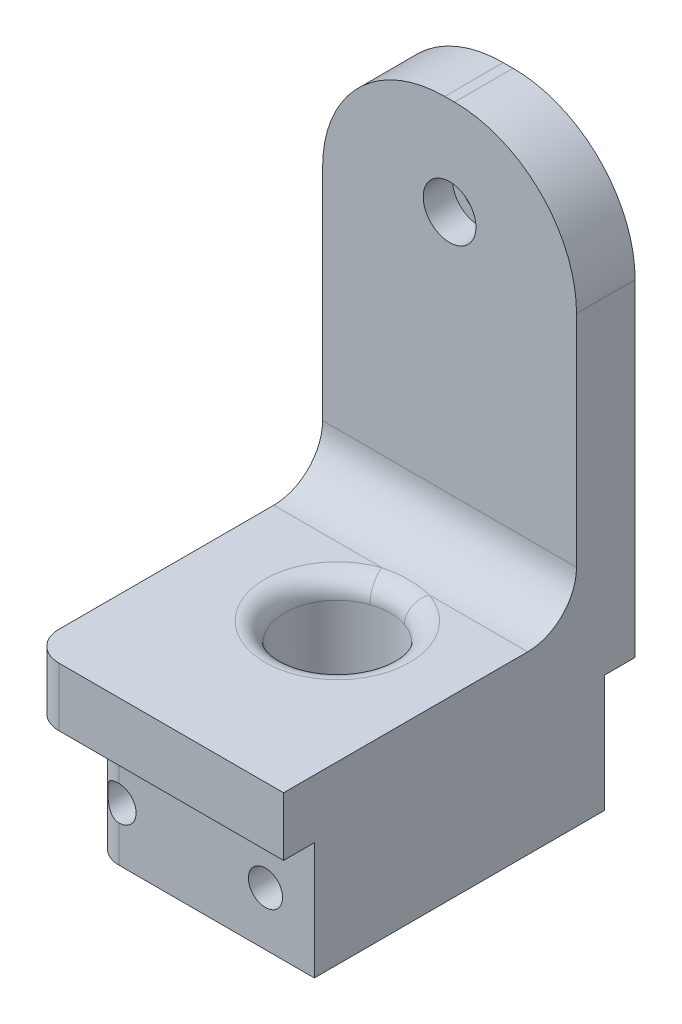
SolidWorks part; units mm, degrees
ref_plane "Front Plane" through (0, 0, 0) normal (0, 0, 1) x (1, 0, 0)
ref_plane "Top Plane" through (0, 0, 0) normal (0, 1, 0) x (1, 0, 0)
ref_plane "Right Plane" through (0, 0, 0) normal (1, 0, 0) x (0, 0, -1)
sketch "Sketch1" plane through (0, -44, 0) normal (0, 1, 0) x (1, 0, 0)
  line L0 (50.2641, 25) -> (50.2641, 28) construction
  line L1 (50.2641, -8) -> (50.2641, 28)
  line L2 (50.2641, -8) -> (27.2641, -8) construction
  line L3 (50.2641, -8) -> (27.2641, -8)
  line L4 (24.2641, -5) -> (24.2641, 25)
  line L5 (27.2641, 28) -> (50.2641, 28)
  arc A0 (27.2641, 28) -> (24.2641, 25) centre (27.2641, 25) ccw construction
  arc A1 (24.2641, -5) -> (27.2641, -8) centre (27.2641, -5) ccw construction
  arc A2 (27.2641, 28) -> (24.2641, 25) centre (27.2641, 25) ccw
  arc A3 (24.2641, -5) -> (27.2641, -8) centre (27.2641, -5) ccw
extrude "Boss-Extrude1" add sketch "Sketch1" along normal blind 6
sketch "Sketch2" plane through (0, -38, 0) normal (0, 1, 0) x (1, 0, 0)
  line L0 (24.2641, 25) -> (24.2641, -5) construction
  line L1 (50.2641, 28) -> (24.2641, 28)
  line L2 (50.2641, 28) -> (50.2641, 22)
  line L3 (50.2641, 22) -> (24.2641, 22)
  line L4 (24.2641, 28) -> (24.2641, 22)
  dimension "D1" = 6
extrude "Boss-Extrude2" add sketch "Sketch2" along normal blind 40
fillet "Fillet1" radius 12.5 2 edges at (24.2641, 2, -25) (50.2641, 2, -25)
sketch "Sketch3" plane through (0, 0, -22) normal (0, 0, 1) x (1, 0, 0)
  circle A0 centre (37.2641, -8) radius 2.7
extrude "Cut-Extrude1" cut sketch "Sketch3" against normal through all
sketch "Sketch4" plane through (0, -44, 0) normal (0, -1, 0) x (1, 0, 0)
  line L3 (50.2641, 4.85) -> (50.2641, -24.85)
  line L6 (50.2641, -24.85) -> (30.2641, -24.85)
  line L7 (27.4141, 2) -> (27.4141, -22)
  line L8 (30.2641, 4.85) -> (50.2641, 4.85)
  arc A4 (27.4141, -22) -> (30.2641, -24.85) centre (30.2641, -22) ccw
  arc A5 (30.2641, 4.85) -> (27.4141, 2) centre (30.2641, 2) ccw
extrude "Boss-Extrude3" add sketch "Sketch4" along normal blind 12
fillet "Fillet2" radius 5 1 edges at (37.2641, -38, -22)
sketch "Sketch5" plane through (0, 0, -24.85) normal (0, 0, -1) x (-1, 0, 0)
  circle A0 centre (-45.2641, -50.5) radius 1.75
  circle A1 centre (-30.2641, -50.5) radius 1.75
extrude "Cut-Extrude2" cut sketch "Sketch5" against normal through all
sketch "Sketch6" plane through (0, -38, 0) normal (0, -1, 0) x (1, 0, 0)
  line L2 (24.2641, -28) -> (27.2641, -28)
  line L3 (24.2641, -25) -> (24.2641, -28)
  line L4 (24.2641, -28) -> (27.2641, -28)
  line L5 (24.2641, -25) -> (24.2641, -28)
  arc A1 (24.2641, -25) -> (27.2641, -28) centre (27.2641, -25) ccw
  arc A2 (24.2641, -25) -> (27.2641, -28) centre (27.2641, -25) ccw
  dimension "D1" = 0
extrude "Cut-Extrude3" cut sketch "Sketch6" against normal through all
sketch "Sketch7" plane through (0, -56, 0) normal (0, -1, 0) x (1, 0, 0)
  line L0 (32.0141, 4.85) -> (30.2641, 4.85) construction
  line L1 (47.0141, 4.85) -> (43.5141, 4.85) construction
  line L2 (32.0141, 4.85) -> (30.2641, 4.85) construction
  line L3 (47.0141, 4.85) -> (43.5141, 4.85) construction
  line L4 (30.2641, 4.85) -> (30.2641, -10.0084) construction
  line L5 (45.2641, 4.85) -> (45.2641, -10.0084) construction
  line L6 (30.2641, -10.0084) -> (45.2641, -10.0084) construction
  circle A0 centre (37.7641, -10.0084) radius 5.4
extrude "Cut-Extrude4" cut sketch "Sketch7" against normal up to surface (18 mm away) up to face at (35.1398, -38, -2.4757)
fillet "Fillet3" radius 2 2 edges at (43.1641, -56, -10.0084) (32.3641, -38, -10.0084)
sketch "Sketch8" plane through (0, 0, -28) normal (0, 0, -1) x (-1, 0, 0)
  circle A0 centre (-37.2641, -8) radius 2.7 construction
  circle A1 centre (-37.2641, -8) radius 2.7
  circle A2 centre (-37.2641, -8) radius 1.6
extrude "Boss-Extrude4" add sketch "Sketch8" against normal blind 3
